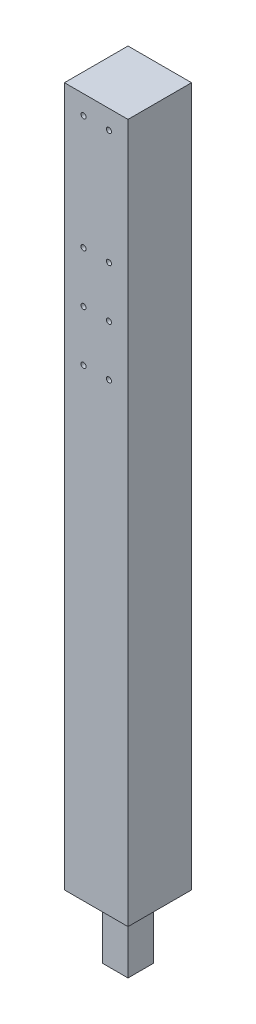
SolidWorks part; units mm, degrees
material "Balsa"
ref_plane "Plan de face" through (0, 0, 0) normal (0, 0, 1) x (1, 0, 0)
ref_plane "Plan de dessus" through (0, 0, 0) normal (0, 1, 0) x (1, 0, 0)
ref_plane "Plan de droite" through (0, 0, 0) normal (1, 0, 0) x (0, 0, -1)
sketch "Sketch2" plane through (0, 0, 0) normal (0, 1, 0) x (1, 0, 0)
  line L1 (0, 0) -> (25, 0)
  line L2 (0, 0) -> (0, 25)
  line L3 (0, 25) -> (25, 25)
  line L4 (25, 0) -> (25, 25)
  dimension "D1" = 25
  dimension "D2" = 25
extrude "Boss-Extrude1" add sketch "Sketch2" along normal blind 300
sketch "Sketch3" plane through (0, 0, 0) normal (0, 0, 1) x (1, 0, 0)
  line L0 (12.5, 300) -> (12.5, 0) construction
  line L1 (7.5, 300) -> (7.5, 0) construction
  line L4 (0, 0) -> (25, 0)
  line L5 (25, 0) -> (25, 300)
  line L6 (25, 300) -> (0, 300)
  line L7 (0, 300) -> (0, 0)
  line L8 (0, 0) -> (25, 0)
  line L10 (25, 300) -> (0, 300)
  circle A0 centre (7.5, 292.5) radius 1
  circle A1 centre (7.5, 247.5) radius 1
  circle A2 centre (7.5, 227.5) radius 1
  circle A3 centre (7.5, 207.5) radius 1
  circle A4 centre (17.5, 292.5) radius 1
  circle A5 centre (17.5, 247.5) radius 1
  circle A6 centre (17.5, 227.5) radius 1
  circle A7 centre (17.5, 207.5) radius 1
  dimension "D3" = 7.5
  dimension "D4" = 2
  dimension "D5" = 2
  dimension "D6" = 45
  dimension "D7" = 2
  dimension "D8" = 2
  dimension "D9" = 20
  dimension "D10" = 20
  dimension "D2" = 5
  dimension "D1" = 0
extrude "Cut-Extrude1" cut sketch "Sketch3" against normal through all contours A0 | A4 | A1 | A5 | A2 | A6 | A7 | A3
sketch "Sketch4" plane through (0, 0, 0) normal (-1, 0, 0) x (0, 0, 1)
  line L0 (-25, 25) -> (-17.5, 25)
  line L1 (-12.5, 0) -> (-12.5, 300) construction
  line L2 (-17.5, 25) -> (-17.5, 0)
  line L3 (-25, 300) -> (0, 300) construction
  line L4 (-25, 0) -> (0, 0)
  line L5 (0, 0) -> (0, 300)
  line L6 (0, 300) -> (-25, 300)
  line L7 (-25, 300) -> (-25, 0)
  line L8 (-25, 0) -> (0, 0)
  line L11 (-25, 25) -> (-25, 0)
  line L12 (-25, 300) -> (0, 300)
  line L13 (0, 25) -> (0, 0)
  line L14 (0, 25) -> (-7.5, 25)
  line L15 (-7.5, 25) -> (-7.5, 0)
  line M9 (-25, 0) -> (0, 0)
  line M10 (0, 0) -> (0, 300)
  line M12 (-25, 300) -> (-25, 0)
  dimension "D2" = 25
  dimension "D3" = 5
  dimension "D1" = 0
extrude "Cut-Extrude2" cut sketch "Sketch4" against normal through all and the other way through all contours L2 L0 M12 M9 | L14 L15 L8 M10 region at (0, 12.5, -21.25) region at (0, 12.5, -3.75)
sketch "Sketch5" plane through (0, 0, -17.5) normal (0, 0, -1) x (-1, 0, 0)
  line L0 (-17.5, 25) -> (-17.5, 0)
  line L1 (-12.5, 25) -> (-12.5, 0) construction
  line L2 (-7.5, 25) -> (-7.5, 0)
  line L4 (0, 0) -> (0, 25)
  line L5 (0, 25) -> (-25, 25)
  line L6 (-25, 25) -> (-25, 0)
  line L7 (-25, 0) -> (0, 0)
  line L8 (0, 0) -> (0, 25)
  line L9 (0, 25) -> (-25, 25)
  line L10 (-25, 25) -> (-25, 0)
  line L11 (-25, 0) -> (0, 0)
  line M7 (0, 0) -> (0, 25)
  line M8 (0, 25) -> (-25, 25)
  line M9 (-25, 25) -> (-25, 0)
  line M10 (-25, 0) -> (0, 0)
  dimension "D2" = 5
  dimension "D1" = 0
extrude "Cut-Extrude3" cut sketch "Sketch5" against normal through all contours L0 M8 M9 M10 | L2 M8 M10 M7 region at (21.25, 12.5, -17.5) region at (3.75, 12.5, -17.5)
